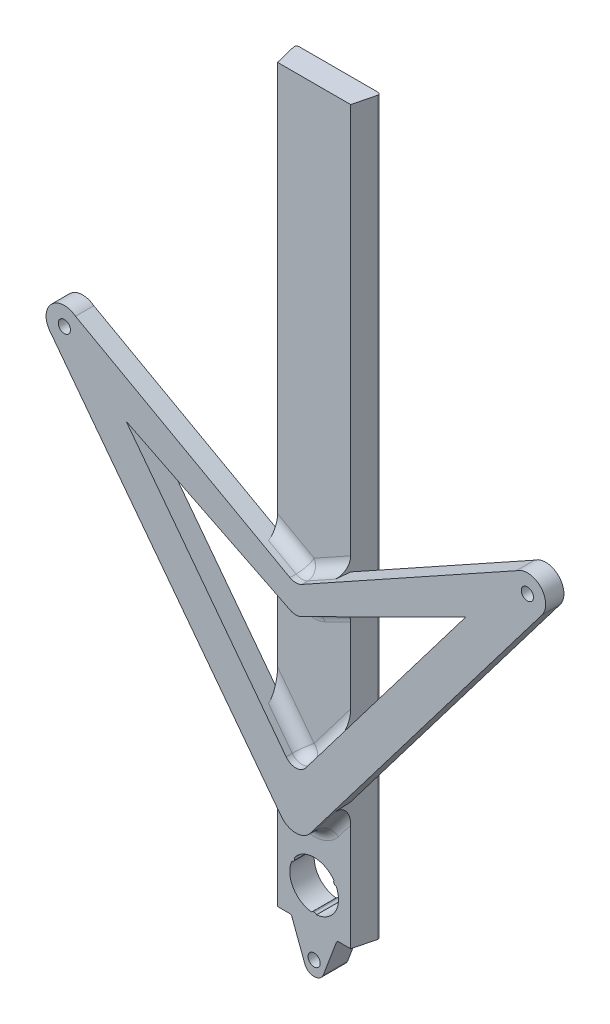
SolidWorks part; units mm, degrees
ref_plane "前视基准面" through (0, 0, 0) normal (0, 0, 1) x (1, 0, 0)
ref_plane "上视基准面" through (0, 0, 0) normal (0, 1, 0) x (1, 0, 0)
ref_plane "右视基准面" through (0, 0, 0) normal (1, 0, 0) x (0, 0, -1)
sketch "草图1" plane through (0, 0, 0) normal (0, 1, 0) x (1, 0, 0)
  line L0 (-3, 0) -> (3, 0)
  line L1 (3, 0) -> (3.5, 2)
  line L2 (3.5, 2) -> (-3.5, 2)
  line L3 (0, 2) -> (0, 0) construction
  line L4 (-3, 0) -> (-3.5, 2)
  dimension "D1" = 3
  dimension "D2" = 3.5
  dimension "D3" = 2
extrude "凸台-拉伸3" add sketch "草图1" along normal blind 60
sketch "草图2" plane through (0, 0, 0) normal (0, -1, 0) x (1, 0, 0)
  line L0 (0, 0) -> (0, -2) construction
  line L1 (-3, 0) -> (3, 0) construction
  line L2 (3.5, -2) -> (-3.5, -2) construction
  line L3 (0, -1) -> (3.5875, -1) construction
  line L5 (-0.75, -2) -> (0.75, -2)
  line L6 (-0.75, -2) -> (-0.75, 0)
  line L7 (-0.75, 0) -> (0.75, 0)
  line L8 (0.75, -2) -> (0.75, 0)
  line L9 (-0.75, -2) -> (0.75, 0) construction
  line L10 (-0.75, 0) -> (0.75, -2) construction
  dimension "D1" = 1.5
extrude "凸台-拉伸4" add sketch "草图2" along normal blind 3
sketch "草图3" plane through (0, 0, 0) normal (0, 0, 1) x (1, 0, 0)
  line L0 (0, 0) -> (0, -3) construction
  line L1 (0.75, -3) -> (-0.75, -3) construction
  circle A0 centre (0, -2.2905) radius 0.5
  dimension "D1" = 1
extrude "切除-拉伸1" cut sketch "草图3" against normal through all
sketch "草图4" plane through (0, 0, 0) normal (0, 0, 1) x (1, 0, 0)
  line L0 (-1.875, 0) -> (-0.75, -3)
  line L1 (-3, 0) -> (-0.75, 0) construction
  line L2 (0, 0) -> (0, -3) construction
  line L3 (0.75, -3) -> (-0.75, -3) construction
  line L4 (1.875, 0) -> (0.75, -3)
  line L7 (-1.875, 0) -> (-0.75, 0)
  line L8 (-0.75, 0) -> (-0.75, -3)
  line L9 (1.875, 0) -> (0.75, 0)
  line L10 (0.75, 0) -> (0.75, -3)
extrude "凸台-拉伸6" add sketch "草图4" against normal up to surface (2 mm away) up to face at (0.5, -2.2905, -2)
sketch "草图5" plane through (0, 0, -2) normal (0, 0, -1) x (-1, 0, 0)
  line L0 (-1.875, 0) -> (1.875, 0) construction
  line L1 (0, 0) -> (0, 3) construction
  circle A0 centre (0, 3) radius 2
  dimension "D1" = 4
  dimension "D3" = 3
extrude "切除-拉伸2" cut sketch "草图5" against normal through all
fillet "圆角1" radius 0.2 2 edges at (-1.875, 0, -1) (1.875, 0, -1)
fillet "圆角2" radius 0.2 2 edges at (-3.5, 30, -2) (3.5, 30, -2)
ref_plane "基准面1" through (0, 1, 0) normal (0, 1, 0) x (1, 0, 0)
sketch "草图6" plane through (0, 1, 0) normal (0, 1, 0) x (1, 0, 0)
  line L0 (0, 2) -> (0, 0) construction
  line L1 (3.2438, 2) -> (-3.2438, 2) construction
  line L2 (-3, 0) -> (3, 0) construction
  line L3 (-0.2, 2) -> (0.2, 2)
  line L4 (-0.2, 2) -> (-0.2, 0)
  line L5 (-0.2, 0) -> (0.2, 0)
  line L6 (0.2, 2) -> (0.2, 0)
  line L7 (-0.2, 2) -> (0.2, 0) construction
  line L8 (-0.2, 0) -> (0.2, 2) construction
  point P5 (0, 1)
  dimension "D1" = 0.4
extrude "凸台-拉伸7" add sketch "草图6" along normal blind 0.1
fillet "圆角3" radius 0.2 2 edges at (0.2, 1.1, -1) (-0.2, 1.1, -1)
pattern_circular "阵列(圆周)3" count 3 over 360 about axis through (0, 3, 0) along (0, 0, -1) of "圆角3", "凸台-拉伸7" reverse direction yes
sketch "草图7" plane through (0, 0, 0) normal (0, 0, 1) x (1, 0, 0)
  line L0 (-0.445, 23.0797) -> (-13.9299, 29.7807)
  line L3 (-13.9299, 29.7807) -> (0, 11.4435)
  line L5 (-20.1942, 33.0676) -> (-1.1942, 8.0676)
  line L6 (-18.0821, 35.1615) -> (0, 25.1191)
  line L7 (20.1942, 33.0676) -> (1.1942, 8.0676)
  line L8 (0, 11.4435) -> (0, 73.0075) construction
  line L9 (0.445, 23.0797) -> (13.9299, 29.7807)
  line L11 (18.0821, 35.1615) -> (0, 25.1191)
  line L12 (13.9299, 29.7807) -> (0, 11.4435)
  arc A0 (-1.1942, 8.0676) -> (1.1942, 8.0676) centre (0, 8.9752) ccw
  arc A1 (20.1942, 33.0676) -> (18.0821, 35.1615) centre (19, 33.9752) ccw
  arc A2 (-0.445, 23.0797) -> (0.445, 23.0797) centre (0, 23.9752) ccw
  arc A3 (1.1942, 8.0676) -> (-1.1942, 8.0676) centre (0, 8.9752) cw
  arc A4 (-20.1942, 33.0676) -> (-18.0821, 35.1615) centre (-19, 33.9752) cw
  line M29 (3, 0) -> (3, 60)
  line M31 (-3, 60) -> (-3, 0)
  dimension "D1" = 3
  dimension "D4" = 3
  dimension "D6" = 2
  dimension "D5" = 15
extrude "凸台-拉伸8" add sketch "草图7" along normal blind 1.5 contours L7 A1 L11 L9 L12 M29 | L8 A2 L9 L11 M29 | A2 L8 L6 L0 M31 | A4 L5 L3 L0 L6 M31 | L5 A0 L7 L12 L3 M29 M31 region at (-1.5222, 24.7925, 0) region at (-10.8961, 25.5159, 0) region at (1.5222, 24.7925, 0) region at (0, 11.0587, 0) region at (10.8961, 25.5159, 0)
sketch "草图8" plane through (0, 0, 1.5) normal (0, 0, 1) x (1, 0, 0)
  line L0 (0, 25.1191) -> (0, 47.7901) construction
  circle A0 centre (-19, 33.9752) radius 0.5
  circle A1 centre (19, 33.9752) radius 0.5
  dimension "D1" = 1
extrude "切除-拉伸3" cut sketch "草图8" against normal through all
sketch "草图9" plane through (0, 0, -2) normal (0, 0, -1) x (-1, 0, 0)
  line L0 (-0.75, -3) -> (0.75, -3)
  arc A0 (-0.75, -3) -> (0.75, -3) centre (0, -2.6545) ccw
extrude "凸台-拉伸9" add sketch "草图9" against normal blind 2
fillet "圆角4" radius 1 2 edges at (0, 11.4435, 0.75) (0, 25.1191, 0.75)
fillet "圆角5" radius 1 12 edges at (2.0971, 9.2556, 0) (0, 7.4752, 0) (1.7225, 23.7145, 0) (0, 22.9752, 0) (1.7428, 26.087, 0) (0, 25.2629, 0) (1.8981, 13.9422, 0) (0, 12.0967, 0) (-2.0971, 9.2556, 0) (-1.7225, 23.7145, 0) (-1.7428, 26.087, 0) (-1.8981, 13.9422, 0)
